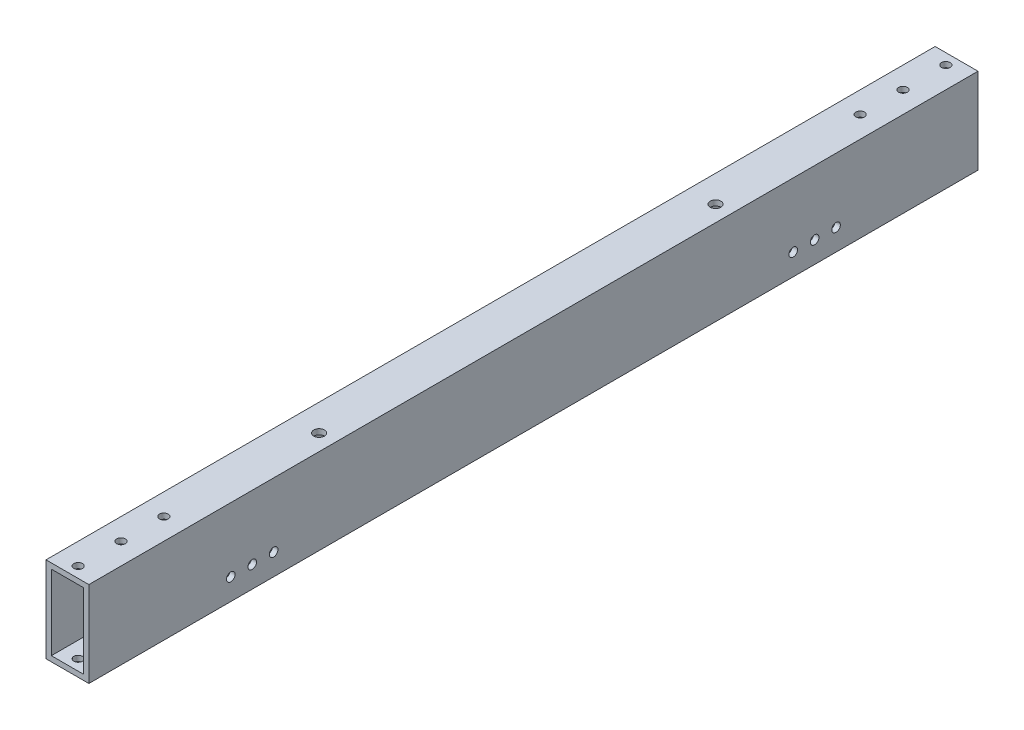
SolidWorks part; units mm, degrees
material "6061-T6 (SS)"
ref_plane "Front" through (0, 0, 0) normal (0, 0, 1) x (1, 0, 0)
ref_plane "Top" through (0, 0, 0) normal (0, 1, 0) x (1, 0, 0)
ref_plane "Right" through (0, 0, 0) normal (1, 0, 0) x (0, 0, -1)
sketch "Sketch1" plane through (0, 0, 0) normal (0, 0, 1) x (1, 0, 0)
  line L1 (-12.7, -25.4) -> (12.7, -25.4)
  line L2 (-12.7, -25.4) -> (-12.7, 25.4)
  line L3 (-12.7, 25.4) -> (12.7, 25.4)
  line L4 (12.7, -25.4) -> (12.7, 25.4)
  line L5 (-12.7, -25.4) -> (12.7, 25.4) construction
  line L6 (-12.7, 25.4) -> (12.7, -25.4) construction
  point P0 (0, 0)
  dimension "D1" = 25.4
  dimension "D2" = 50.8
extrude "Extrude-Thin1" add sketch "Sketch1" along normal blind 527.05 thin thin type one direction reverse wall 3.175
hole_wizard "#10 Clearance Hole1" positions "Sketch2" profile "Sketch3" hole size "#10" standard "ANSI Inch" end condition through all
sketch "Sketch2" plane through (0, 25.4, 0) normal (0, 1, 0) x (1, 0, 0)
  line L0 (12.7, -527.05) -> (-12.7, -527.05) construction
  line L1 (-12.7, -527.05) -> (-12.7, 0) construction
  point P0 (0, -520.7)
  point P2 (0, -495.3)
  point P4 (0, -469.9)
  point P6 (0, -6.35)
  point P8 (0, -31.75)
  point P10 (0, -57.15)
  dimension "D1" = 6.35
  dimension "D2" = 12.7
  dimension "D3" = 25.4
  dimension "D4" = 25.4
  dimension "D5" = 6.35
  dimension "D6" = 25.4
  dimension "D7" = 25.4
sketch "Sketch3" plane through (0, 25.4, 520.7) normal (1, 0, 0) x (0, 0, 1)
  line L0 (0, 0) -> (0, 50.8)
  line L1 (0, 50.8) -> (2.5527, 50.8)
  line L2 (2.5527, 50.8) -> (2.5527, 0)
  line L5 (2.5527, 0) -> (0, 0)
  line L11 (0, -6.35) -> (0, 107.95) construction
  dimension "Thru Hole Dia." = 5.1054
  dimension "Thru Hole Depth" = 50.8
sketch "Sketch6" plane through (0, -25.4, 0) normal (0, -1, 0) x (-1, 0, 0)
  point P0 (3.175, -70.358)
  point P3 (-3.175, -95.758)
  point P6 (3.175, -121.158)
  point P9 (-3.175, -146.558)
  point P12 (3.175, -171.958)
  point P15 (-3.175, -197.358)
  point P22 (-3.175, -248.158)
  point P25 (3.175, -273.558)
  point P28 (-3.175, -298.958)
  point P31 (3.175, -324.358)
  point P34 (-3.175, -349.758)
  point P37 (3.175, -375.158)
  point P40 (-3.175, -400.558)
  point P43 (3.175, -425.958)
  point P46 (-3.175, -451.358)
  point P54 (3.175, -222.758)
hole_wizard "1/8 (0.13) Diameter Hole1" positions "Sketch6" profile "Sketch5" hole size "1/8" standard "ANSI Inch" end condition up to next
sketch "Sketch5" plane through (-3.175, -25.4, 70.358) normal (1, 0, 0) x (0, 0, -1)
  line L0 (0, 0) -> (0, 3.175)
  line L1 (0, 3.175) -> (1.651, 3.175)
  line L2 (1.651, 3.175) -> (1.651, 0)
  line L5 (1.651, 0) -> (0, 0)
  line L11 (0, -6.35) -> (0, 107.95) construction
  dimension "Thru Hole Dia." = 3.302
  dimension "Thru Hole Depth" = 3.175
sketch "Sketch9" plane through (0, 25.4, 0) normal (0, 1, 0) x (1, 0, 0)
  line L0 (12.7, 0) -> (-12.7, 0) construction
  line L1 (12.7, -527.05) -> (12.7, 0) construction
  line L2 (12.7, -527.05) -> (-12.7, -527.05) construction
  point P0 (3.175, -146.05)
  point P2 (3.175, -381)
  dimension "D1" = 146.05
  dimension "D2" = 9.525
  dimension "D3" = 146.05
hole_wizard "1/4 (0.25) Diameter Hole1" positions "Sketch9" profile "Sketch8" hole size "1/4" standard "ANSI Inch"
sketch "Sketch8" plane through (3.175, 25.4, 146.05) normal (1, 0, 0) x (0, 0, 1)
  line L0 (0, 0) -> (0, 12.6265)
  line L1 (0, 12.6265) -> (3.175, 10.7188)
  line L2 (3.175, 10.7188) -> (3.175, 0)
  line L5 (3.175, 0) -> (0, 0)
  line L10 (0, 12.6265) -> (-3.175, 10.7188) construction
  line L11 (0, -6.35) -> (0, 107.95) construction
  dimension "Hole Dia." = 6.35
  dimension "Hole Depth" = 10.7188
  dimension "Drill Angle" = 118
sketch "Sketch12" plane through (-12.7, 0, 0) normal (-1, 0, 0) x (0, 0, 1)
  point P44 (84.1375, -12.7)
  point P47 (96.8375, -12.7)
  point P50 (109.5375, -12.7)
  point P53 (417.5125, -12.7)
  point P56 (430.2125, -12.7)
  point P59 (442.9125, -12.7)
hole_wizard "CBORE for #10 Socket Head Cap Screw1" positions "Sketch12" profile "Sketch11" counterbore size "#10" standard "ANSI Inch" end condition through all
sketch "Sketch11" plane through (-12.7, -12.7, 84.1375) normal (0, 1, 0) x (0, 0, 1)
  line L0 (0, 0) -> (0, 25.4)
  line L1 (0, 25.4) -> (2.5527, 25.4)
  line L3 (2.5527, 25.4) -> (2.5527, 8.001)
  line L4 (2.5527, 8.001) -> (4.7625, 8.001)
  line L5 (4.7625, 8.001) -> (4.7625, 0)
  line L7 (4.7625, 0) -> (0, 0)
  line L11 (0, -6.35) -> (0, 107.95) construction
  dimension "Thru Hole Dia." = 5.1054
  dimension "Thru Hole Depth" = 25.4
  dimension "C'Bore Dia." = 9.525
  dimension "C'Bore Depth" = 8.001
